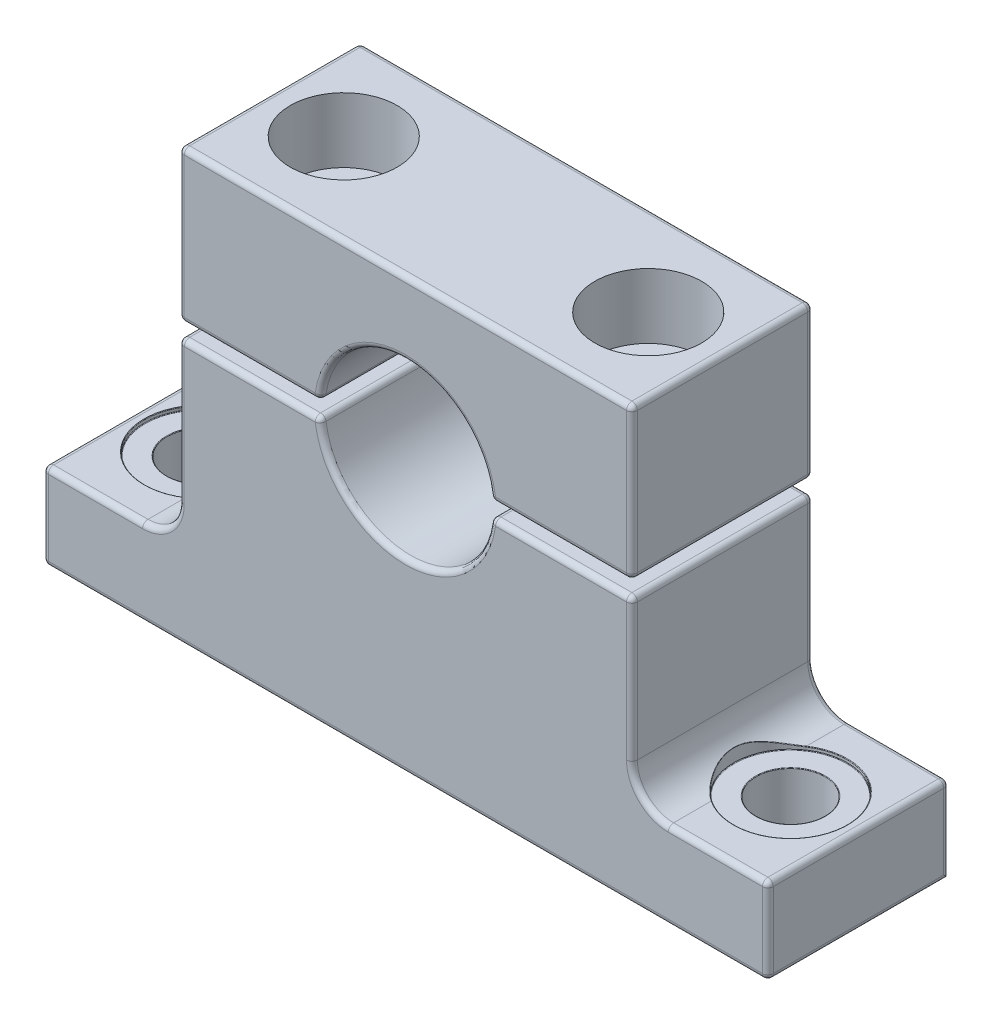
SolidWorks part; units mm, degrees
note: '?' marks a value the reader was unsure of.
material "6061-T6 (SS)"
ref_plane "Front" through (0, 0, 0) normal (0, 0, 1) x (1, 0, 0)
ref_plane "Top" through (0, 0, 0) normal (0, 1, 0) x (1, 0, 0)
ref_plane "Right" through (0, 0, 0) normal (1, 0, 0) x (0, 0, -1)
sketch "Sketch1" plane through (0, 0, 0) normal (0, 0, 1) x (1, 0, 0)
  line L0 (0, 30.1625) -> (0, 0) construction
  line L1 (-25.4, 0) -> (25.4, 0) construction
  line L2 (0, 0) -> (0, 19.05) construction
  line L3 (-20.6375, 0) -> (20.6375, 0) construction
  line L4 (18.2245, 0) -> (23.0505, 0) construction
  line L5 (23.0505, 0) -> (23.0505, 1.27) construction
  line L6 (18.2245, 0) -> (18.2245, 1.27) construction
  line L7 (-18.2245, 0) -> (-18.2245, 1.27) construction
  line L8 (-23.0505, 0) -> (-23.0505, 1.27) construction
  line L9 (-18.2245, 0) -> (-23.0505, 0) construction
  line L10 (-15.875, 19.05) -> (15.875, 19.05) construction
  line L11 (-15.875, 18.542) -> (15.875, 18.542) construction
  line L12 (-15.875, 19.558) -> (15.875, 19.558) construction
  line L13 (17.8435, 0) -> (17.8435, 1.27) construction
  line L14 (23.4315, 0) -> (23.4315, 1.27) construction
  line L15 (-17.8435, 0) -> (-17.8435, 1.27) construction
  line L16 (-23.4315, 0) -> (-23.4315, 1.27) construction
  line L17 (-11.0713, 18.542) -> (11.0713, 18.542) construction
  line L18 (-11.0713, 19.558) -> (11.0713, 19.558) construction
  line L19 (-11.0713, 19.05) -> (11.0713, 19.05) construction
  line L20 (-25.4, 0) -> (-25.4, 6.0325) construction
  line L21 (-25.4, 6.0325) -> (-15.875, 6.0325) construction
  line L22 (-15.875, 18.542) -> (-15.875, 6.0325) construction
  line L23 (-15.875, 19.558) -> (-15.875, 30.1625) construction
  line L24 (-15.875, 30.1625) -> (15.875, 30.1625) construction
  line L25 (25.4, 0) -> (25.4, 6.0325) construction
  line L26 (25.4, 6.0325) -> (15.875, 6.0325) construction
  line L27 (15.875, 18.542) -> (15.875, 6.0325) construction
  line L28 (15.875, 19.558) -> (15.875, 30.1625) construction
  line L29 (0, 30.1625) -> (0, 25.9969) construction
  line L30 (0.3175, 25.9969) -> (-0.3175, 25.9969) construction
  line L31 (15.875, 6.0325) -> (15.875, 0) construction
  line L32 (-20.6375, 0) -> (-20.6375, 6.0325) construction
  line L33 (0, 25.05) -> (15.875, 25.05) construction
  line L34 (0, 13.05) -> (15.875, 13.05) construction
  circle A0 centre (0, 19.05) radius 6 construction
  arc A1 (-18.415, 6.0325) -> (-15.875, 8.5725) centre (-18.415, 8.5725) ccw construction
  arc A2 (18.415, 6.0325) -> (15.875, 8.5725) centre (18.415, 8.5725) cw construction
  point P5 (0, 0)
  point P9 (0, 19.05)
  point P11 (0, 0)
  point P12 (20.6375, 0)
  point P13 (-20.6375, 0)
  point P16 (20.6375, 0)
  point P37 (0, 18.542)
  point P40 (0, 19.558)
  point P60 (0, 25.9969)
  point P64 (20.6375, 6.0325)
  dimension "D1" = 1.27
  dimension "D8" = 6.0325
  dimension "D12" = 0.635
  dimension "Radius" = 2.54
  dimension "D9" = 4.7625
  dimension "D3" = 0.508
  dimension "D4" = 0.381
  dimension "D5" = 0.381
  dimension "D6" = 0.381
  dimension "D7" = 0.381
sketch "Sketch3" plane through (0, 0, 0) normal (0, 0, 1) x (1, 0, 0)
  line L0 (-15.875, 30.1625) -> (15.875, 30.1625) construction
  line L1 (15.875, 19.558) -> (15.875, 30.1625) construction
  line L2 (-15.875, 19.558) -> (15.875, 19.558) construction
  line L3 (-15.875, 19.558) -> (-15.875, 30.1625) construction
  line L4 (-15.875, 18.542) -> (-15.875, 6.0325) construction
  line L5 (-25.4, 6.0325) -> (-15.875, 6.0325) construction
  line L6 (-25.4, 0) -> (-25.4, 6.0325) construction
  line L7 (-25.4, 0) -> (25.4, 0) construction
  line L8 (25.4, 0) -> (25.4, 6.0325) construction
  line L9 (25.4, 6.0325) -> (15.875, 6.0325) construction
  line L10 (15.875, 18.542) -> (15.875, 6.0325) construction
  line L11 (-15.875, 18.542) -> (15.875, 18.542) construction
  line L12 (-15.875, 30.1625) -> (15.875, 30.1625)
  line L13 (15.875, 19.558) -> (15.875, 30.1625)
  line L14 (-15.875, 19.558) -> (-5.9785, 19.558)
  line L15 (-15.875, 19.558) -> (-15.875, 30.1625)
  line L16 (-15.875, 18.542) -> (-15.875, 8.5725)
  line L17 (-25.4, 6.0325) -> (-18.415, 6.0325)
  line L18 (-25.4, 0) -> (-25.4, 6.0325)
  line L19 (-25.4, 0) -> (25.4, 0)
  line L20 (25.4, 0) -> (25.4, 6.0325)
  line L21 (25.4, 6.0325) -> (18.415, 6.0325)
  line L22 (15.875, 18.542) -> (15.875, 8.5725)
  line L23 (-15.875, 18.542) -> (-5.9785, 18.542)
  line L24 (5.9785, 19.558) -> (15.875, 19.558)
  line L25 (5.9785, 18.542) -> (15.875, 18.542)
  arc A0 (-18.415, 6.0325) -> (-15.875, 8.5725) centre (-18.415, 8.5725) ccw construction
  arc A1 (15.875, 8.5725) -> (18.415, 6.0325) centre (18.415, 8.5725) ccw construction
  circle A2 centre (0, 19.05) radius 6 construction
  arc A3 (-18.415, 6.0325) -> (-15.875, 8.5725) centre (-18.415, 8.5725) ccw
  arc A4 (15.875, 8.5725) -> (18.415, 6.0325) centre (18.415, 8.5725) ccw
  arc A5 (5.9785, 19.558) -> (-5.9785, 19.558) centre (0, 19.05) ccw
  arc A6 (-5.9785, 18.542) -> (5.9785, 18.542) centre (0, 19.05) ccw
extrude "Boss-Extrude1" add sketch "Sketch3" against normal blind 12.7
sketch "Sketch4" plane through (0, 0, 0) normal (0, -1, 0) x (1, 0, 0)
  line L0 (-25.4, 0) -> (-25.4, -12.7) construction
  line L1 (-25.4, 0) -> (-15.875, 0) construction
  line L2 (-25.4, -6.35) -> (25.4, -6.35) construction
  line L3 (25.4, -12.7) -> (25.4, 0) construction
  line L4 (-20.6375, 0) -> (-20.6375, -12.7) construction
  line L5 (20.6375, 0) -> (20.6375, -12.7) construction
  line L6 (-25.4, -12.7) -> (25.4, -12.7) construction
  line L7 (0, 0) -> (0, -12.7) construction
  circle A0 centre (-20.6375, -6.35) radius 2.413
  circle A1 centre (20.6375, -6.35) radius 2.413
  point P7 (-25.4, -6.35)
  dimension "D1" = 4.826
extrude "Cut-Extrude1" cut sketch "Sketch4" against normal through all
sketch "Sketch6" plane through (0, 6.0325, 0) normal (0, 1, 0) x (1, 0, 0)
  line L0 (0, 0) -> (0, 12.7) construction
  line L1 (-25.4, 0) -> (25.4, 0) construction
  line L2 (15.875, 12.7) -> (-15.875, 12.7) construction
  circle A1 centre (-20.6375, 6.35) radius 2.413 construction
  circle A2 centre (-20.6375, 6.35) radius 2.413
  circle A4 centre (-20.6375, 6.35) radius 2.794
  circle A5 centre (20.6375, 6.35) radius 2.794
  dimension "D1" = 0.381
sketch "Sketch7" plane through (0, 0, 0) normal (0, 0, 1) x (1, 0, 0)
  line L0 (-25.4, 5.7785) -> (25.4, 5.7785) construction
  line L1 (-15.875, 18.542) -> (-15.875, 0) construction
  line L2 (-25.4, 0) -> (25.4, 0) construction
  line L3 (15.875, 18.542) -> (15.875, 0) construction
  line L5 (-25.4, 0) -> (-25.4, 6.0325) construction
  line L6 (-25.4, 6.0325) -> (-15.875, 6.0325) construction
  line L7 (25.4, 0) -> (25.4, 6.0325) construction
  line L8 (-20.6375, 6.0325) -> (-20.6375, 5.7785) construction
  line L9 (20.6375, 6.0325) -> (20.6375, 5.7785) construction
  line L10 (25.4, 6.0325) -> (15.875, 6.0325) construction
  dimension "D1" = 0.254
sketch "Sketch8" plane through (0, 18.542, 0) normal (0, 1, 0) x (1, 0, 0)
  line L0 (0, 0) -> (0, 12.7) construction
  line L1 (15.875, 12.7) -> (-15.875, 12.7) construction
  circle A0 centre (-20.6375, 6.35) radius 2.794 construction
  circle A1 centre (20.6375, 6.35) radius 2.794 construction
  circle A2 centre (-20.6375, 6.35) radius 2.794 construction
  circle A3 centre (20.6375, 6.35) radius 2.794 construction
  circle A4 centre (-20.6375, 6.35) radius 3.9751
  circle A5 centre (20.6375, 6.35) radius 3.9751
  dimension "CounterBoreID" = 7.9502
extrude "Cut-Extrude3" cut sketch "Sketch8" against normal up to vertex (12.7635 mm away) up to point (-20.6375, 5.7785, 0)
sketch "Sketch10" plane through (0, 30.1625, 0) normal (0, 1, 0) x (1, 0, 0)
  line L0 (-15.875, 12.7) -> (-15.875, 0) construction
  line L1 (15.875, 12.7) -> (15.875, 0) construction
  line L2 (-15.875, 12.7) -> (-15.875, 0) construction
  line L3 (15.875, 12.7) -> (15.875, 0) construction
  line L4 (-14.097, 12.7) -> (-14.097, 0) construction
  line L5 (0, 0) -> (0, 12.7) construction
  line L6 (14.097, 12.7) -> (14.097, 0) construction
  circle A0 centre (-10.668, 6.35) radius 2.0828 construction
  circle A1 centre (10.668, 6.35) radius 2.3368
  circle A2 centre (-10.668, 6.35) radius 2.3368
  circle A3 centre (10.668, 6.35) radius 2.0828 construction
  circle A4 centre (-10.668, 6.35) radius 3.429 construction
  circle A5 centre (10.668, 6.35) radius 3.429 construction
extrude "Cut-Extrude4" cut sketch "Sketch10" against normal through all
ref_plane "Plane1" through (0, 0, -6.35) normal (0, 0, 1) x (1, 0, 0)
sketch "Sketch12" plane through (0, 30.1625, 0) normal (0, 1, 0) x (1, 0, 0)
  line L0 (0, 12.7) -> (0, 0) construction
  circle A0 centre (-10.668, 6.35) radius 3.6195 construction
  circle A1 centre (10.668, 6.35) radius 3.7465
  circle A2 centre (-10.668, 6.35) radius 3.7465
  circle A3 centre (10.668, 6.35) radius 3.6195 construction
  dimension "D2" = 7.493
extrude "Cut-Extrude5" cut sketch "Sketch12" against normal blind 4.5466
sketch "Sketch13" plane through (0, 0, 0) normal (0, 1, 0) x (1, 0, 0)
  line L0 (-10.668, 12.7) -> (-10.668, 0) construction
  line L1 (15.875, 12.7) -> (-15.875, 12.7) construction
  line L2 (0, 12.7) -> (0, 0) construction
  line L3 (10.668, 12.7) -> (10.668, 0) construction
  circle A0 centre (-10.668, 6.35) radius 2.0066 construction
  point P2 (-10.668, 6.35)
  point P9 (-10.668, 12.7)
  point P10 (-10.668, 0)
  point P17 (10.668, 12.7)
  point P18 (10.668, 0)
  dimension "D1" = 4.0132
sketch "Sketch15" plane through (0, 0, -6.35) normal (0, 0, 1) x (1, 0, 0)
  line L0 (-10.668, 12.065) -> (-10.668, 30.1625) construction
  line L1 (-10.668, 30.1625) -> (-14.097, 30.1625) construction
  line L2 (-14.097, 30.1625) -> (-14.097, 25.9969) construction
  line L3 (-14.097, 25.9969) -> (-12.7508, 25.9969) construction
  line L4 (-12.7508, 25.9969) -> (-12.7508, 12.065) construction
  line L5 (-12.7508, 12.065) -> (-10.668, 12.065) construction
  line L8 (-15.875, 30.1625) -> (15.875, 30.1625) construction
  line L9 (-10.668, 12.065) -> (-10.668, 30.1625)
  line L10 (-10.668, 30.1625) -> (-14.097, 30.1625)
  line L11 (-14.097, 30.1625) -> (-14.097, 25.9969)
  line L12 (-14.097, 25.9969) -> (-12.7508, 25.9969)
  line L13 (-12.7508, 25.9969) -> (-12.7508, 12.065)
  line L14 (-12.7508, 12.065) -> (-10.668, 12.065)
  dimension "D2" = 3.429
  dimension "D1" = 4.1656
  dimension "D3" = 2.0828
  dimension "Screw Length" = 18.0975
revolve "Revolve1" [suppressed] add sketch "Sketch15" angle 360 about L9
chamfer "Chamfer1" [suppressed] distance 0.127 angle 45
sketch "Sketch16" [suppressed] plane through (0, 30.1625, 0) normal (0, 1, 0) x (1, 0, 0)
  line L0 (-10.668, 12.7) -> (-10.668, 0) construction
  line L1 (-10.668, 8.4122) -> (-12.4539, 7.3811)
  line L2 (-12.4539, 7.3811) -> (-12.4539, 5.3189)
  line L3 (-12.4539, 5.3189) -> (-10.668, 4.2878)
  line L4 (-10.668, 4.2878) -> (-8.8821, 5.3189)
  line L5 (-8.8821, 5.3189) -> (-8.8821, 7.3811)
  line L6 (-8.8821, 7.3811) -> (-10.668, 8.4122)
  circle A0 centre (-10.668, 6.35) radius 1.7859 construction
  dimension "Hex Size" = 3.5719
extrude "Cut-Extrude6" [suppressed] cut sketch "Sketch16" against normal blind 1.3746
mirror "Mirror1" [suppressed] about plane through (0, 0, 0) normal (1, 0, 0)
fillet "Fillet1" radius 0.381 18 edges at (0, 30.1625, -12.7) (-15.875, 30.1625, -6.35) (-15.875, 24.8603, -12.7) (-15.875, 24.8603, 0) (15.875, 24.8603, -12.7) (15.875, 30.1625, -6.35) (15.875, 24.8603, 0) (0, 30.1625, 0) (15.875, 19.558, -6.35) (10.9267, 19.558, -12.7) (-10.9267, 19.558, -12.7) (-15.875, 19.558, -6.35) (-10.9267, 19.558, 0) (10.9267, 19.558, 0) (0, 25.05, -12.7) (0, 25.05, 0) (5.9785, 19.558, -6.35) (-5.9785, 19.558, -6.35)
fillet "Fillet2" radius 0.381 31 edges at (21.9075, 6.0325, -12.7) (16.6189, 6.7764, -12.7) (15.875, 13.5573, 0) (16.6189, 6.7764, 0) (-21.9075, 6.0325, 0) (-16.6189, 6.7764, 0) (-21.9075, 6.0325, -12.7) (-16.6189, 6.7764, -12.7) (15.875, 13.5573, -12.7) (25.4, 0, -6.35) (25.4, 3.0162, -12.7) (25.4, 6.0325, -6.35) (21.9075, 6.0325, 0) (25.4, 3.0162, 0) (0, 0, 0) (-25.4, 3.0162, -12.7) (-25.4, 0, -6.35) (-25.4, 6.0325, -6.35) (-25.4, 3.0162, 0) (-15.875, 13.5573, 0) (-15.875, 13.5573, -12.7) (15.875, 18.542, -6.35) (-15.875, 18.542, -6.35) (-10.9267, 18.542, 0) (10.9267, 18.542, 0) (10.9267, 18.542, -12.7) (-10.9267, 18.542, -12.7) (0, 13.05, -12.7) (0, 13.05, 0) (5.9785, 18.542, -6.35) (-5.9785, 18.542, -6.35)
fillet "Fillet3" radius 0.0381 8 edges at (-24.6126, 5.7785, -6.35) (24.6126, 5.7785, -6.35) (24.6126, 6.0325, -6.35) (16.6835, 6.7142, -6.7586) (23.0505, 5.7785, -6.35) (-16.6705, 6.7264, -6.0967) (-24.6126, 6.0325, -6.35) (-23.0505, 5.7785, -6.35)
ref_plane "Contact Plane 1" through (0, 0, -6.35) normal (0, 0, -1) x (-1, 0, 0)
ref_plane "Contact Plane 2" through (0, 0, 0) normal (-1, 0, 0) x (0, 0, 1)
ref_plane "Contact Plane 3" through (0, 15.0812, 0) normal (0, 1, 0) x (1, 0, 0)
ref_plane "Contact Plane 4" through (0, 30.1625, 0) normal (0, 1, 0) x (1, 0, 0)
ref_plane "Contact Plane 5" through (0, 0, 0) normal (0, -1, 0) x (-1, 0, 0)
ref_plane "Contact Plane 6" through (25.4, 0, 0) normal (1, 0, 0) x (0, 0, -1)
ref_plane "Contact Plane 7" through (-25.4, 0, 0) normal (-1, 0, 0) x (0, 0, 1)
ref_axis "Center Axis 1" through (0, 54.8037, -6.35) along (0, -1, 0)?
ref_axis "Center Axis 2" through (0, 15.0812, -33.3184) along (0, 0, 1)?
ref_axis "Center Axis 3" through (69.4309, 15.0813, -6.35) along (-1, 0, 0)?
ref_plane "Split Plane" through (0, 19.05, 0) normal (0, 1, 0) x (1, 0, 0)
split "Split1" trim tools "Split Plane" bodies to split 117 118 resulting bodies 137 138
equation "\"D8@Sketch1\"=\"Oall Ht@Sketch1\"*.20"
equation "\"D1@Sketch4\"= \"HoldDia@Sketch1\""
equation "\"D1@Cut-Extrude5\"=\"HeadDp@Sketch1\"+.015"
equation "\"D1@Sketch15\"=\"HeadDp@Sketch1\""
equation "\"D3@Sketch15\"=\"ThrdDia@Sketch10\"*.5"
equation "\"D1@Cut-Extrude6\"= \"HeadDp@Sketch1\"*.33"
equation "\"D2@Sketch12\"=\"Head Dia@Sketch10\"+.025"
equation "\"D2@Sketch15\"=\"Head Dia@Sketch10\"*.50"
